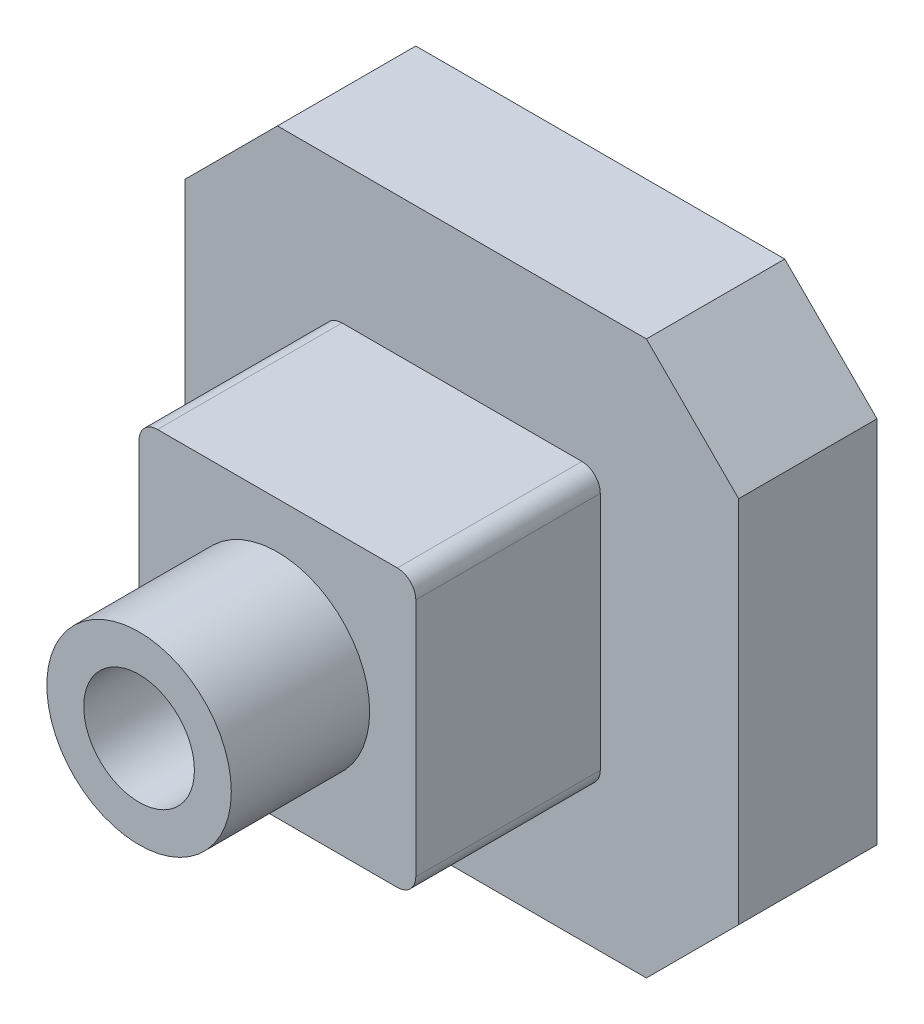
SolidWorks part; units mm, degrees
material "Chrome Stainless Steel"
ref_plane "Front" through (0, 0, 0) normal (0, 0, 1) x (1, 0, 0)
ref_plane "Top" through (0, 0, 0) normal (0, 1, 0) x (1, 0, 0)
ref_plane "Right" through (0, 0, 0) normal (1, 0, 0) x (0, 0, -1)
sketch "Sketch1" plane through (0, 0, 0) normal (0, 0, 1) x (1, 0, 0)
  line L1 (-30, 30) -> (30, 30)
  line L2 (-30, 30) -> (-30, -30)
  line L3 (-30, -30) -> (30, -30)
  line L4 (30, 30) -> (30, -30)
  line L5 (-30, 30) -> (30, -30) construction
  line L6 (-30, -30) -> (30, 30) construction
  point P0 (0, 0)
  dimension "D1" = 60
  dimension "D2" = 60
extrude "Boss-Extrude1" add sketch "Sketch1" along normal blind 15
sketch "Sketch2" plane through (0, 0, 15) normal (0, 0, 1) x (1, 0, 0)
  line L1 (-15, 15) -> (15, 15)
  line L2 (-15, 15) -> (-15, -15)
  line L3 (-15, -15) -> (15, -15)
  line L4 (15, 15) -> (15, -15)
  line L5 (-15, 15) -> (15, -15) construction
  line L6 (-15, -15) -> (15, 15) construction
  point P0 (0, 0)
  dimension "D1" = 30
  dimension "D2" = 30
extrude "Boss-Extrude2" add sketch "Sketch2" along normal blind 20
sketch "Sketch3" plane through (0, 0, 35) normal (0, 0, 1) x (1, 0, 0)
  circle A0 centre (0, 0) radius 10
  dimension "D1" = 20
extrude "Boss-Extrude3" add sketch "Sketch3" along normal blind 15
sketch "Sketch4" plane through (0, 0, 50) normal (0, 0, 1) x (1, 0, 0)
  circle A0 centre (0, 0) radius 6
  dimension "D1" = 12
extrude "Cut-Extrude1" cut sketch "Sketch4" against normal through all
chamfer "Chamfer1" distance 10 angle 45 4 edges at (30, 30, 7.5) (30, -30, 7.5) (-30, -30, 7.5) (-30, 30, 7.5)
fillet "Fillet1" radius 2 4 edges at (15, -15, 25) (15, 15, 25) (-15, 15, 25) (-15, -15, 25)
shell "Shell1" thickness 3 removed face at (6, 0, 0)
